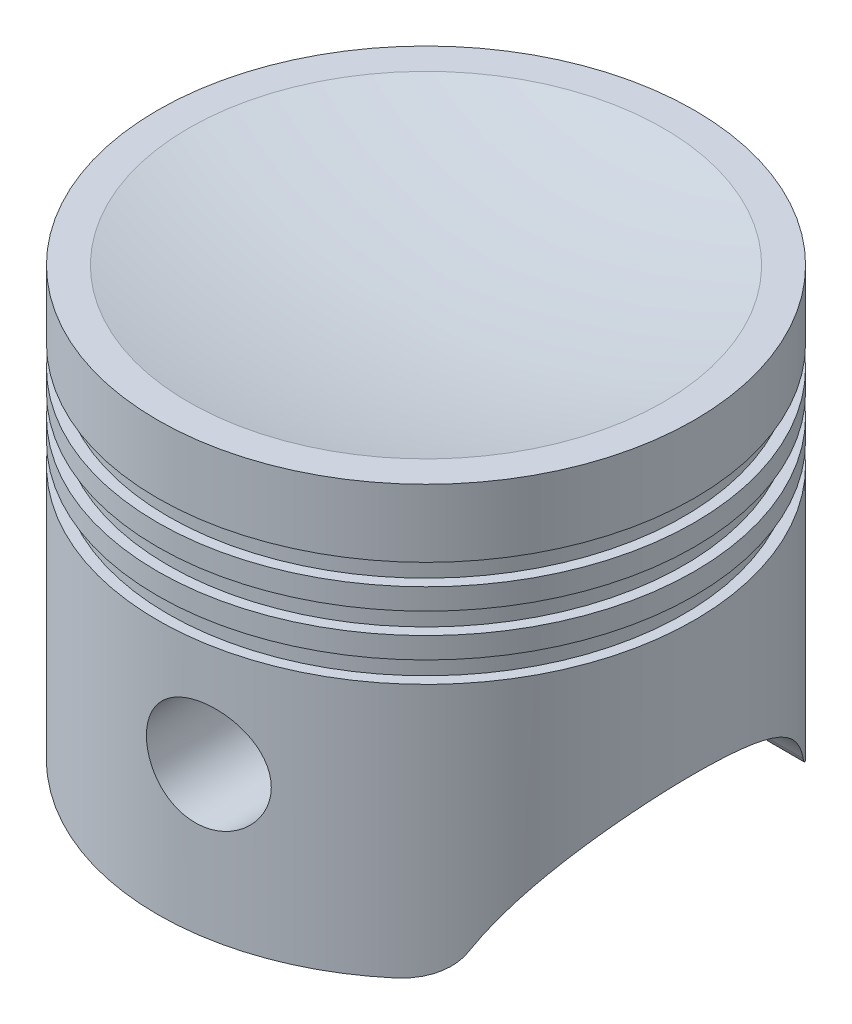
SolidWorks part; units mm, degrees
ref_plane "Front Plane" through (0, 0, 0) normal (0, 0, 1) x (1, 0, 0)
ref_plane "Top Plane" through (0, 0, 0) normal (0, 1, 0) x (1, 0, 0)
ref_plane "Right Plane" through (0, 0, 0) normal (1, 0, 0) x (0, 0, -1)
sketch "Sketch1" plane through (0, 0, 0) normal (0, 0, 1) x (1, 0, 0)
  line L0 (0, 19) -> (0, 0)
  line L1 (0, 0) -> (57.15, 0)
  line L2 (57.15, 0) -> (57.15, -75.3)
  line L3 (57.15, -75.3) -> (63.5, -75.3)
  line L4 (63.5, -75.3) -> (63.5, 26)
  line L5 (63.5, 26) -> (56.15, 26)
  arc A1 (0, 19) -> (56.15, 26) centre (-1.981, 263.592) ccw
  dimension "D7" = 244.6
  dimension "D1" = 19
  dimension "D2" = 101.3
  dimension "D3" = 6.35
  dimension "D4" = 7.35
  dimension "D5" = 63.5
  dimension "D6" = 7
revolve "Revolve1" add sketch "Sketch1" angle 360 about L0
sketch "Sketch2" plane through (0, 0, 0) normal (0, 0, 1) x (1, 0, 0)
  line L0 (63.5, -75.3) -> (63.5, 26) construction
  line L1 (61, 10) -> (63.5, 10)
  line L2 (61, 10) -> (61, 5)
  line L3 (61, 5) -> (63.5, 5)
  line L4 (63.5, 10) -> (63.5, 5)
  line L5 (0, 0) -> (0, 50.0646) construction
  dimension "D1" = 5
  dimension "D2" = 2.5
  dimension "D3" = 5
revolve "Cut-Revolve1" cut sketch "Sketch2" angle 360 about L5
pattern_linear "LPattern1" count 3 spacing 10 along (0, -1, 0) of "Cut-Revolve1"
sketch "Sketch3" plane through (0, 0, 0) normal (0, 0, 1) x (1, 0, 0)
  circle A0 centre (10, -40) radius 12.7
  point P2 (0, 0)
  point P4 (0, 0)
  point P5 (4.4756, -39.7488)
  point P6 (0, 0)
  dimension "D1" = 25.4
  dimension "D2" = 10
  dimension "D3" = 40
extrude "Cut-Extrude1" cut sketch "Sketch3" against normal through all both and the other way through all
sketch "Sketch4" plane through (0, 0, 0) normal (1, 0, 0) x (0, 0, -1)
  line L0 (-63.5, -75.3) -> (63.5, -75.3) construction
  arc A0 (-42, -75.3) -> (42, -75.3) centre (0, -91.4555) cw
  point P7 (0, -46.4555)
  dimension "D2" = 45
  dimension "D1" = 42
extrude "Cut-Extrude3" cut sketch "Sketch4" against normal through all and the other way through all flip side to cut
fillet "Fillet1" radius 10 4 edges at (43.1917, -75.3, -42) (-43.1917, -75.3, -42) (43.1917, -75.3, 42) (-43.1917, -75.3, 42)
sketch "Sketch5" plane through (0, 0, 0) normal (0, 0, 1) x (1, 0, 0)
  circle A0 centre (10, -40) radius 12.7 construction
  circle A1 centre (10, -40) radius 12.7
  circle A2 centre (10, -40) radius 15.2
  dimension "D1" = 2.5
extrude "Boss-Extrude1" add sketch "Sketch5" along normal up to surface (29.304 mm away) from offset 30 up to face at (21.4991, -45.3908, -59.7498)
mirror "Mirror1" about plane through (0, 0, 0) normal (0, 0, 1) of "Boss-Extrude1"
